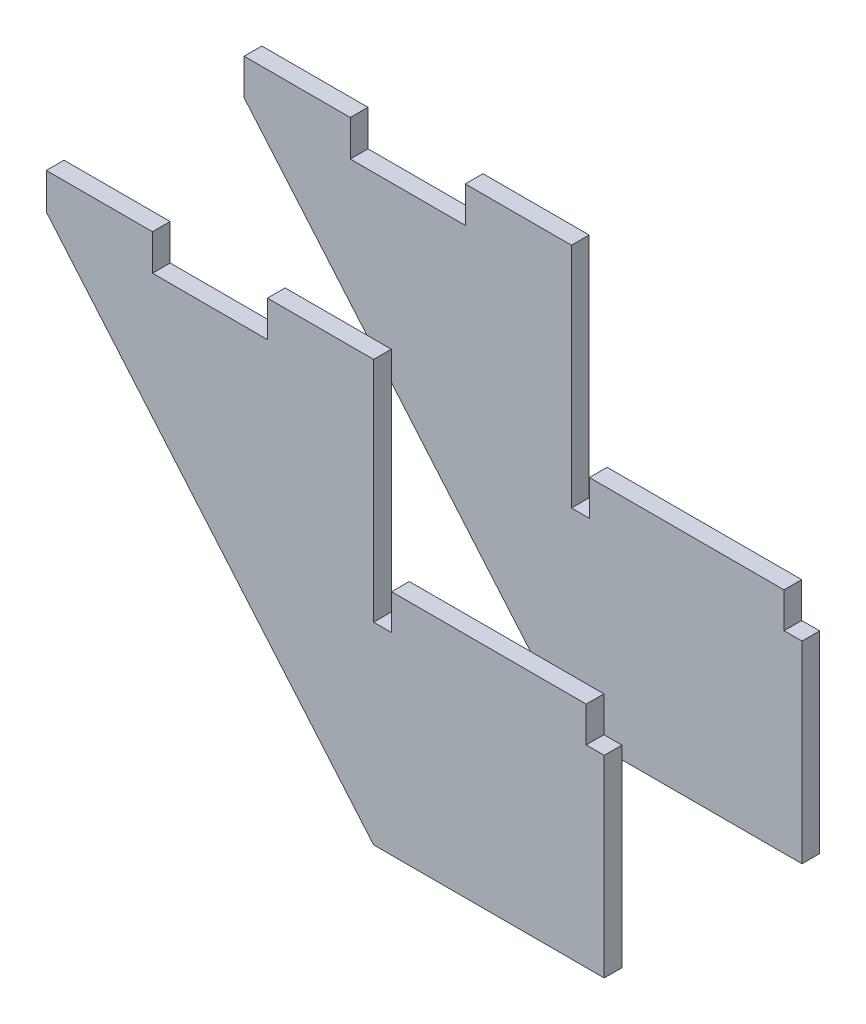
SolidWorks part; units mm, degrees
note: The reader was unsure of these and kept them because the rebuilt part matched: shared geometry of "Sketch1<2>".
material "Gillfab4009"
ref_plane "Front Plane" through (0, 0, 0) normal (0, 0, 1) x (1, 0, 0)
ref_plane "Top Plane" through (0, 0, 0) normal (0, 1, 0) x (1, 0, 0)
ref_plane "Right Plane" through (0, 0, 0) normal (1, 0, 0) x (0, 0, -1)
sketch "Sketch1" plane through (0, 0, 0) normal (0, 0, 1) x (1, 0, 0)
  line L0 (-210.16, -2161.2189) -> (-200, -2161.2189)
  line L1 (-79.84, -2161.2189) -> (-79.84, -2270.2189)
  line L2 (-79.84, -2270.2189) -> (-210.16, -2270.2189)
  line L3 (-210.16, -2270.2189) -> (-395.16, -2052.9116)
  line L4 (-332.7218, -2052.9116) -> (-408.9218, -2052.9116) construction
  line L5 (-335.16, -2052.9116) -> (-270.16, -2052.9116)
  line L6 (-134.539, -2052.9116) -> (-332.7218, -2052.9116) construction
  line L7 (-210.16, -2052.9116) -> (-210.16, -2161.2189)
  line L8 (-200, -2161.2189) -> (-200, -2141.2189)
  line L9 (-200, -2052.9116) -> (-200, -2161.2189) construction
  line L10 (-200, -2141.2189) -> (-90, -2141.2189)
  line L11 (-90, -2052.9116) -> (-90, -2161.2189) construction
  line L12 (-90, -2141.2189) -> (-90, -2161.2189)
  line L13 (-90, -2161.2189) -> (-79.84, -2161.2189)
  line L14 (-395.16, -2052.9116) -> (-395.16, -2032.5916)
  line L15 (-395.16, -2032.5916) -> (-335.16, -2032.5916)
  line L16 (-335.16, -2032.5916) -> (-335.16, -2052.9116)
  line L17 (-210.16, -2052.9116) -> (-210.16, -2032.5916)
  line L18 (-210.16, -2032.5916) -> (-270.16, -2032.5916)
  line L19 (-270.16, -2032.5916) -> (-270.16, -2052.9116)
  line L20 (-270.16, -2032.5916) -> (-335.16, -2032.5916) construction
  line L21 (-90, -2161.2189) -> (-200, -2161.2189) construction
  dimension "D1" = 110
  dimension "D2" = 20
  dimension "D3" = 60
  dimension "D4" = 185
extrude "Boss-Extrude1" add sketch "Sketch1" along normal blind 10 from surface at 236.8927
extrude "Boss-Extrude2" add sketch "Sketch1<2>" against normal blind 10 from surface separate body
sketch "Sketch1<2>" plane through (0, 0, 0) normal (0, 0, 1) x (1, 0, 0) same geometry as "Sketch1"
